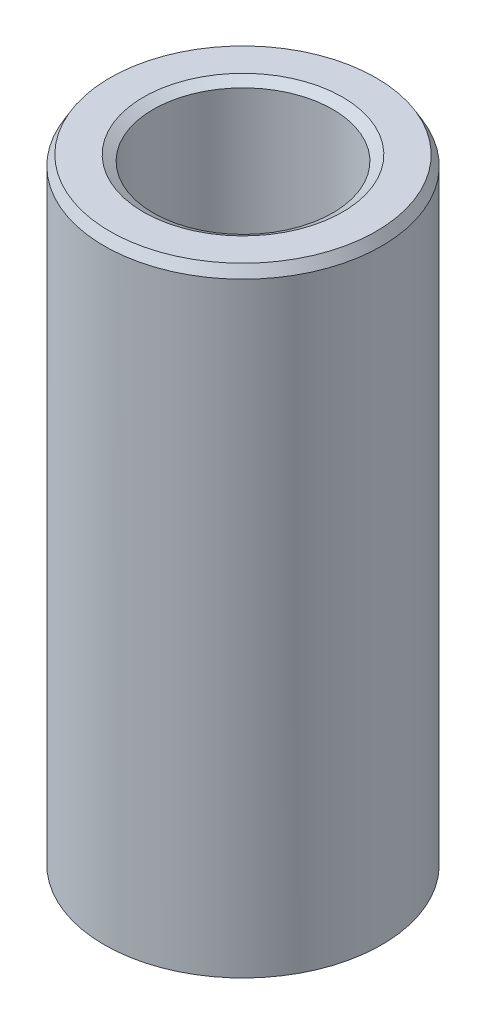
SolidWorks part; units mm, degrees
ref_plane "Front Plane" through (0, 0, 0) normal (0, 0, 1) x (1, 0, 0)
ref_plane "Top Plane" through (0, 0, 0) normal (0, 1, 0) x (1, 0, 0)
ref_plane "Right Plane" through (0, 0, 0) normal (1, 0, 0) x (0, 0, -1)
sketch "Sketch1" plane through (0, 0, 0) normal (0, 1, 0) x (1, 0, 0)
  circle A0 centre (0, 0) radius 10
  dimension "SLEEVE_OD" = 20
extrude "Boss-Extrude1" add sketch "Sketch1" along normal blind 44.7325
sketch "Sketch2" plane through (0, 0, 0) normal (0, 1, 0) x (1, 0, 0)
  circle A0 centre (0, 0) radius 6.47
  dimension "BORE_D" = 12.94
extrude "Cut-Extrude1" cut sketch "Sketch2" along normal through all
chamfer "Chamfer1" distance 0.7081 angle 30 4 edges at (0, 44.7325, 6.47) (0, 0, 6.47) (0, 0, 10) (0, 44.7325, 10) first distance on face at (0, 44.7325, 6.47) first distance on face at (0, 0, 6.47) first distance on face at (0, 44.7325, 10)
